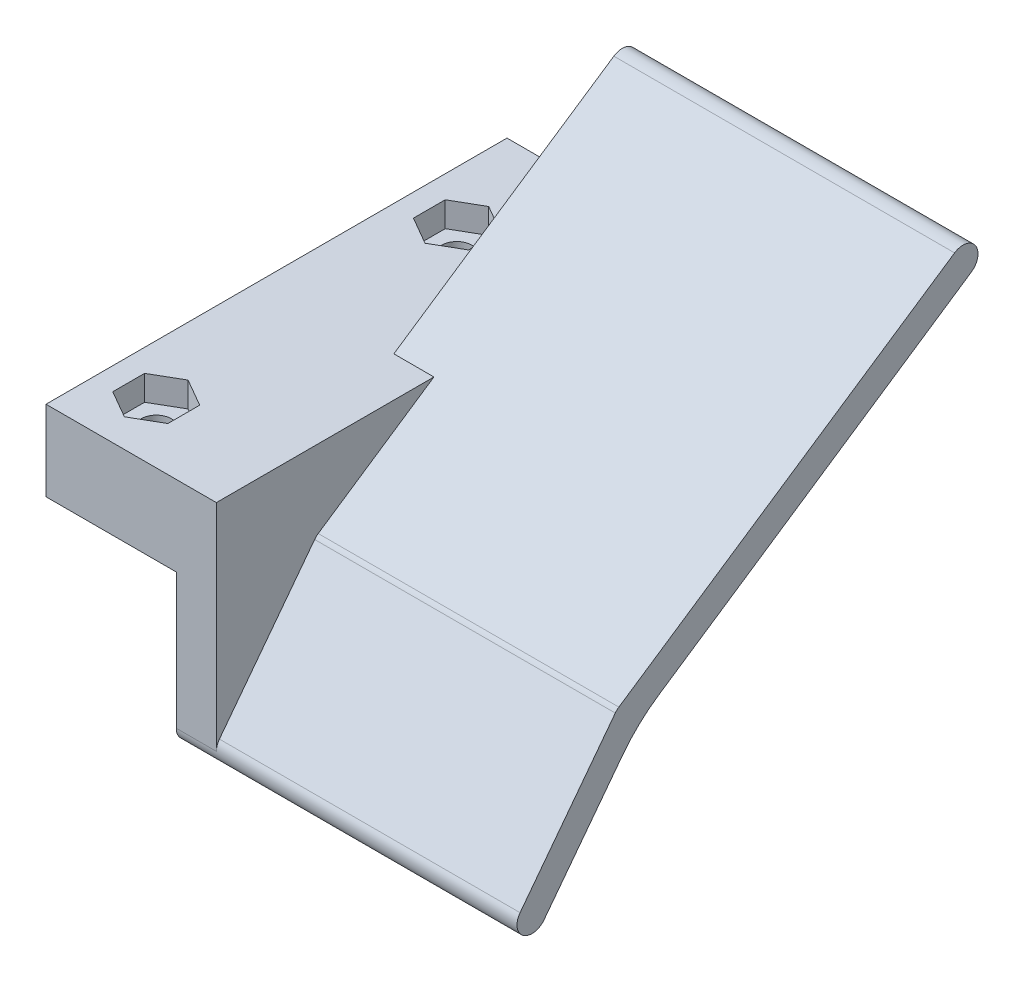
SolidWorks part; units mm, degrees
ref_plane "前视基准面" through (0, 0, 0) normal (0, 0, 1) x (1, 0, 0)
ref_plane "上视基准面" through (0, 0, 0) normal (0, 1, 0) x (1, 0, 0)
ref_plane "右视基准面" through (0, 0, 0) normal (1, 0, 0) x (0, 0, -1)
other "Configuration Table"
sketch "草图1" plane through (0, 0, 0) normal (0, 1, 0) x (1, 0, 0)
  line L0 (0, 0) -> (0, 39.426) construction
  line L1 (56, 0) -> (69, 0)
  line L2 (0, 0) -> (56, 0) construction
  line L3 (0, 0) -> (0, -46) construction
  line L4 (0, -46) -> (56, -46) construction
  line L5 (56, 0) -> (56, -46)
  line L6 (69, 0) -> (69, -46)
  line L7 (69, -46) -> (56, -46)
  line L8 (61, -10) -> (61, -40) construction
  circle A0 centre (61, -10) radius 1.5
  circle A1 centre (61, -40) radius 1.5
  dimension "D4" = 3
  dimension "D5" = 3
  dimension "D1" = 46
  dimension "D2" = 13
  dimension "D3" = 5
  dimension "D6" = 30
  dimension "D7" = 10
  dimension "D8" = 61
extrude "凸台-拉伸1" add sketch "草图1" against normal blind 8
sketch "草图2" plane through (0, 0, 0) normal (0, 1, 0) x (1, 0, 0)
  line L0 (69, -46) -> (69, 0) construction
  line L1 (69, -46) -> (69, 0)
  line L2 (69, 0) -> (73, 0)
  line L3 (73, 0) -> (73, -46)
  line L4 (73, -46) -> (69, -46)
  dimension "D1" = 4
extrude "凸台-拉伸2" add sketch "草图2" along normal blind 15 and the other way blind 23
sketch "草图4" plane through (73, 0, 0) normal (1, 0, 0) x (0, 0, -1)
  line L0 (-1.5, 13.5) -> (-35, -9) construction
  line L1 (0, 15) -> (-1.5, 15) construction
  line L2 (0, 15) -> (0, 13.5) construction
  line L3 (0, 13.5) -> (-1.5, 13.5) construction
  line L4 (0, -23) -> (0, 15)
  line L5 (0, 15) -> (-46, 15)
  line L6 (-46, 15) -> (-46, -23)
  line L7 (-46, -23) -> (0, -23)
  line L8 (0, -23) -> (0, 15) construction
  line L9 (0, 15) -> (-46, 15) construction
  line L10 (-46, 15) -> (-46, -23) construction
  line L11 (-46, -23) -> (0, -23) construction
  line L12 (-1.5, 15) -> (-1.5, 13.5) construction
  line L13 (-46, -23) -> (-44.5, -23) construction
  line L14 (-46, -23) -> (-46, -21.5) construction
  line L15 (-46, -21.5) -> (-44.5, -21.5) construction
  line L16 (-44.5, -23) -> (-44.5, -21.5) construction
  line L19 (-0.6637, 12.2548) -> (-34.1637, -10.2452)
  line L22 (-2.3363, 14.7452) -> (-35.8363, -7.7548)
  line L23 (-35, -9) -> (-44.5, -21.5) construction
  line L24 (-33.8058, -9.9076) -> (-43.3058, -22.4076)
  line L25 (-36.1942, -8.0924) -> (-45.6942, -20.5924)
  arc A4 (-0.6637, 12.2548) -> (-2.3363, 14.7452) centre (-1.5, 13.5) ccw
  arc A5 (-35.8363, -7.7548) -> (-34.1637, -10.2452) centre (-35, -9) ccw
  arc A6 (-33.8058, -9.9076) -> (-36.1942, -8.0924) centre (-35, -9) ccw
  arc A7 (-45.6942, -20.5924) -> (-43.3058, -22.4076) centre (-44.5, -21.5) ccw
  point P10 (-18.25, 2.25)
  point P16 (-39.75, -15.25)
  dimension "D8" = 11
  dimension "D9" = 14
  dimension "D6" = 1.5
  dimension "D7" = 1.5
  dimension "D1" = 0
extrude "凸台-拉伸3" add sketch "草图4" along normal blind 30 contours A6 L24 L19 A4 L22 | L24 A6 A5 L19 | L25 A7 L24 L19 A5 region at (73, 2.9072, 17.2715) region at (73, -16.1884, 40.4633) region at (73, -9.0005, 34.9995)
sketch "草图5" plane through (73, 0, 0) normal (1, 0, 0) x (0, 0, -1)
  line L0 (0, 13.5) -> (0, 15) construction
  line L1 (0, 15) -> (-1.5, 15) construction
  line L2 (-46, -21.5) -> (-46, -23) construction
  line L3 (-46, -23) -> (-44.5, -23) construction
  line L4 (-46, 0) -> (0, 0) construction
  line L5 (-33.9566, -10.1062) -> (-43.3058, -22.4076) construction
  line L6 (-44.5, -23) -> (0, -23) construction
  line L7 (0, -23) -> (0, 13.5) construction
  line L8 (-2.3363, 14.7452) -> (-35.8363, -7.7548) construction
  line L9 (-46, 0) -> (0, 0) construction
  line L10 (-43.3058, -22.4076) -> (-33.9566, -10.1062) construction
  line L11 (-33.9566, -10.1062) -> (-0.6637, 12.2548) construction
  line L12 (-1.5, 15) -> (-46, 15) construction
  line L13 (-46, 15) -> (-46, -21.5) construction
  line L15 (-35.8363, -7.7548) -> (-2.3363, 14.7452) construction
  line L16 (0, 13.5) -> (0, 15)
  line L17 (0, 15) -> (-1.5, 15)
  line L18 (-46, -21.5) -> (-46, -23)
  line L19 (-46, -23) -> (-44.5, -23)
  line L21 (-33.9566, -10.1062) -> (-43.3058, -22.4076)
  line L22 (-44.5, -23) -> (0, -23)
  line L23 (0, -23) -> (0, -8)
  line L24 (-2.3363, 14.7452) -> (-24.2903, 0)
  line L25 (-24.2903, 0) -> (-46, 0)
  line L26 (-43.3058, -22.4076) -> (-33.9566, -10.1062)
  line L27 (-33.9566, -10.1062) -> (-30.8208, -8)
  line L28 (-1.5, 15) -> (-46, 15)
  line L29 (-46, 15) -> (-46, 0)
  line L31 (-24.2903, 0) -> (-2.3363, 14.7452)
  line L32 (-46, -23) -> (-46, -8) construction
  line L33 (-46, -8) -> (0, -8) construction
  line L34 (0, -8) -> (0, -23) construction
  line L35 (0, -23) -> (-46, -23) construction
  line L37 (-46, 0) -> (-46, 15) construction
  line L38 (-46, 15) -> (0, 15) construction
  line L39 (0, 15) -> (0, 0) construction
  line L40 (-46, -23) -> (-46, -21.5)
  line L41 (-30.8208, -8) -> (0, -8)
  line L42 (0, -8) -> (0, -23)
  line L43 (0, -23) -> (-46, -23)
  line L45 (-46, 0) -> (-46, 15)
  line L46 (-46, 15) -> (0, 15)
  line L47 (0, 15) -> (0, 13.5)
  line L49 (-30.8208, -8) -> (-33.9566, -10.1062)
  arc A0 (0, 13.5) -> (-1.5, 15) centre (-1.5, 13.5) ccw construction
  arc A1 (-46, -21.5) -> (-44.5, -23) centre (-44.5, -21.5) ccw construction
  arc A3 (-44.5, -23) -> (-43.3058, -22.4076) centre (-44.5, -21.5) ccw construction
  arc A5 (-45.6942, -20.5924) -> (-43.3058, -22.4076) centre (-44.5, -21.5) ccw construction
  arc A6 (-0.6637, 12.2548) -> (-2.3363, 14.7452) centre (-1.5, 13.5) ccw construction
  arc A7 (-1.5, 15) -> (-2.3363, 14.7452) centre (-1.5, 13.5) ccw construction
  arc A10 (0, 13.5) -> (-1.5, 15) centre (-1.5, 13.5) ccw
  arc A11 (-46, -21.5) -> (-44.5, -23) centre (-44.5, -21.5) ccw
  arc A13 (-44.5, -23) -> (-43.3058, -22.4076) centre (-44.5, -21.5) ccw
  arc A15 (-46, -21.5) -> (-43.3058, -22.4076) centre (-44.5, -21.5) ccw
  arc A16 (0, 13.5) -> (-2.3363, 14.7452) centre (-1.5, 13.5) ccw
  arc A17 (-1.5, 15) -> (-2.3363, 14.7452) centre (-1.5, 13.5) ccw
  arc M3 (-2.3363, 14.7452) -> (-1.5, 15) centre (-1.5, 13.5) cw
  line M4 (-1.5, 15) -> (-46, 15)
  line M5 (-46, 15) -> (-46, -21.5)
  line M9 (-35.8363, -7.7548) -> (-2.3363, 14.7452)
extrude "切除-拉伸1" cut sketch "草图5" against normal up to next contours L25 M9 M3 M4 M5 | A13 L22 L23 L41 L27 L21 | A11 L18 L19 | A10 L16 L17 region at (73, 14.6649, 0.3351) region at (73, -15.8958, 19.1362) region at (73, -22.6649, 45.6649) region at (73, 8.3494, 28.9286)
fillet "圆角1" radius 15 1 edges at (86, -10.1062, 33.9566)
sketch "草图6" plane through (0, 0, 0) normal (0, 1, 0) x (1, 0, 0)
  line L0 (61, -10) -> (61, -40) construction
  line L1 (63.75, -11.5877) -> (63.75, -8.4123)
  line L2 (63.75, -8.4123) -> (61, -6.8246)
  line L3 (61, -6.8246) -> (58.25, -8.4123)
  line L4 (58.25, -8.4123) -> (58.25, -11.5877)
  line L5 (58.25, -11.5877) -> (61, -13.1754)
  line L6 (61, -13.1754) -> (63.75, -11.5877)
  line L7 (61, -43.1754) -> (63.75, -41.5877)
  line L8 (63.75, -41.5877) -> (63.75, -38.4123)
  line L9 (63.75, -38.4123) -> (61, -36.8246)
  line L10 (61, -36.8246) -> (58.25, -38.4123)
  line L11 (58.25, -38.4123) -> (58.25, -41.5877)
  line L12 (58.25, -41.5877) -> (61, -43.1754)
  circle A0 centre (61, -40) radius 1.5 construction
  circle A1 centre (61, -10) radius 1.5 construction
  circle A2 centre (61, -40) radius 1.5 construction
  circle A3 centre (61, -10) radius 1.5 construction
  circle A4 centre (61, -10) radius 2.75 construction
  circle A5 centre (61, -40) radius 2.75 construction
  dimension "D1" = 5.5
  dimension "D2" = 5.5
extrude "切除-拉伸2" cut sketch "草图6" against normal blind 2.5
